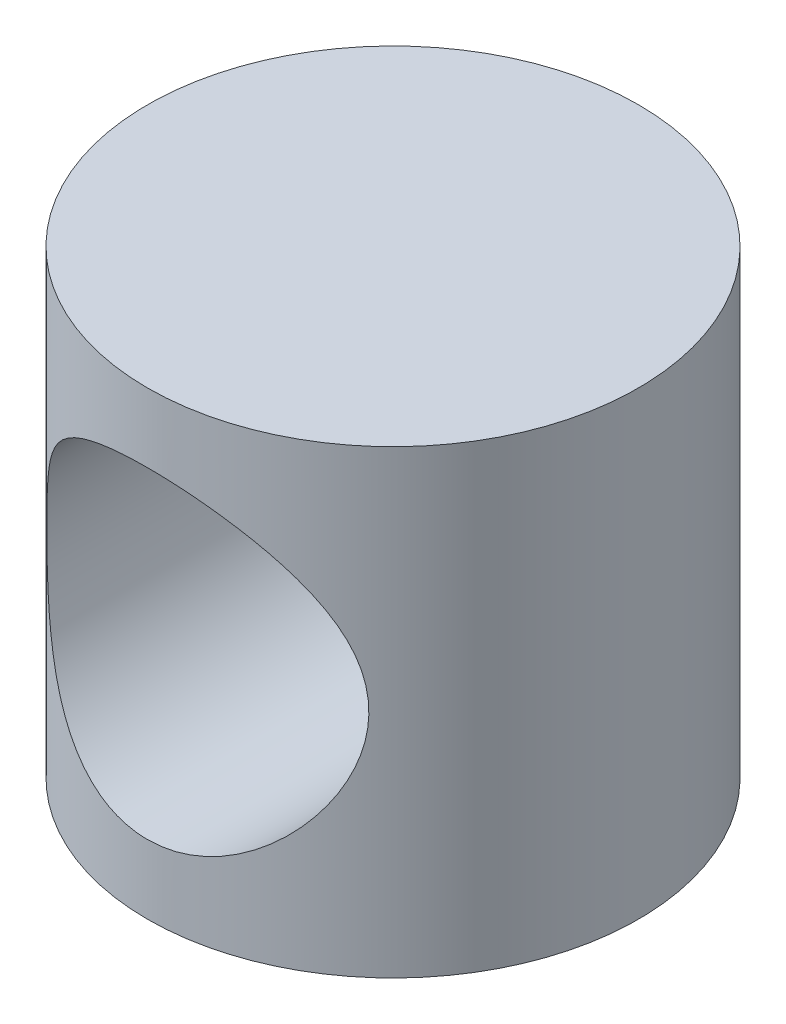
SolidWorks part; units mm, degrees
ref_plane "Front Plane" through (0, 0, 0) normal (0, 0, 1) x (1, 0, 0)
ref_plane "Top Plane" through (0, 0, 0) normal (0, 1, 0) x (1, 0, 0)
ref_plane "Right Plane" through (0, 0, 0) normal (1, 0, 0) x (0, 0, -1)
sketch "Sketch1" plane through (0, 0, 0) normal (0, 1, 0) x (1, 0, 0)
  circle A1 centre (0, 0) radius 3.2
  dimension "D1" = 6.4
extrude "Boss-Extrude1" add sketch "Sketch1" along normal blind 6
sketch "Sketch2" plane through (0, 0, 0) normal (0, 0, 1) x (1, 0, 0)
  line L0 (0, 0) -> (0, 6) construction
  line L3 (-3.2, 0) -> (3.2, 0) construction
  line L4 (3.2, 6) -> (-3.2, 6) construction
  circle A0 centre (0, 3) radius 2.1
  dimension "D1" = 4.2
extrude "Cut-Extrude1" cut sketch "Sketch2" against normal blind 10 and the other way blind 10
